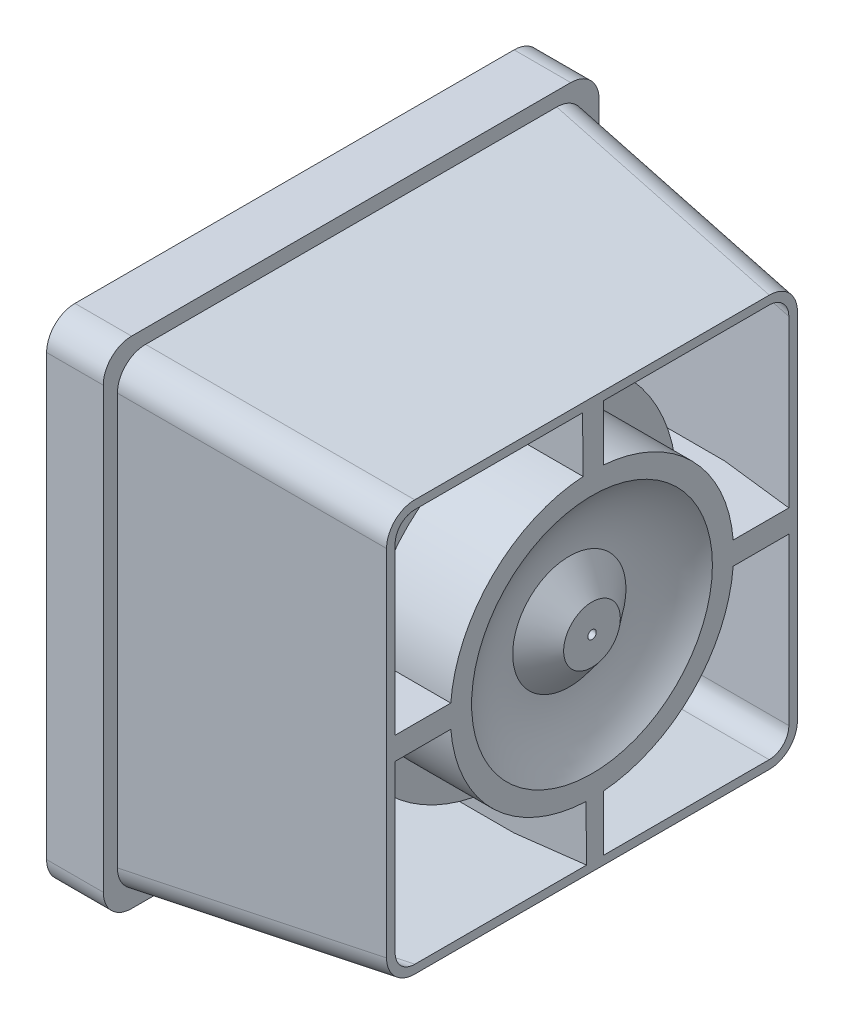
SolidWorks part; units mm, degrees
ref_plane "Front Plane" through (0, 0, 0) normal (0, 0, 1) x (1, 0, 0)
ref_plane "Top Plane" through (0, 0, 0) normal (0, 1, 0) x (1, 0, 0)
ref_plane "Right Plane" through (0, 0, 0) normal (1, 0, 0) x (0, 0, -1)
sketch "Sketch1" plane through (0, 0, 0) normal (1, 0, 0) x (0, 0, -1)
  line L1 (-8.25, -8.25) -> (8.25, -8.25)
  line L2 (-8.25, -8.25) -> (-8.25, 8.25)
  line L3 (-8.25, 8.25) -> (8.25, 8.25)
  line L4 (8.25, -8.25) -> (8.25, 8.25)
  line L5 (-8.25, -8.25) -> (8.25, 8.25) construction
  line L6 (-8.25, 8.25) -> (8.25, -8.25) construction
  point P0 (0, 0)
  dimension "D1" = 16.5
ref_plane "Plane1" through (8.5, 0, 0) normal (-1, 0, 0) x (0, 0, 1)
sketch "Sketch2" plane through (8.5, 0, 0) normal (-1, 0, 0) x (0, 0, 1)
  line L1 (-7.25, -7.25) -> (7.25, -7.25)
  line L2 (-7.25, -7.25) -> (-7.25, 7.25)
  line L3 (-7.25, 7.25) -> (7.25, 7.25)
  line L4 (7.25, -7.25) -> (7.25, 7.25)
  line L5 (-7.25, -7.25) -> (7.25, 7.25) construction
  line L6 (-7.25, 7.25) -> (7.25, -7.25) construction
  point P0 (0, 0)
  dimension "D1" = 14.5
loft "Loft1" add profiles "Sketch1", "Sketch2" connector at (0, -8.25, 8.25) connector at (8.5, -7.25, 7.25)
fillet "Fillet1" radius 1 4 edges
shell "Shell4" thickness 0.3 removed face at (8.5, 0, 0) removed face at (0, 0, 0)
sketch "Sketch3" plane through (0, 0, 0) normal (1, 0, 0) x (0, 0, -1)
  line L1 (-8.75, -8.75) -> (8.75, -8.75)
  line L2 (-8.75, -8.75) -> (-8.75, 8.75)
  line L3 (-8.75, 8.75) -> (8.75, 8.75)
  line L4 (8.75, -8.75) -> (8.75, 8.75)
  line L5 (-8.75, -8.75) -> (8.75, 8.75) construction
  line L6 (-8.75, 8.75) -> (8.75, -8.75) construction
  point P0 (0, 0)
  dimension "D1" = 17.5
extrude "Boss-Extrude1" add sketch "Sketch3" against normal blind 2
fillet "Fillet2" radius 1 4 edges at (-1, -8.75, -8.75) (-1, -8.75, 8.75) (-1, 8.75, 8.75) (-1, 8.75, -8.75)
sketch "Sketch5" plane through (0, 0, 0) normal (0, 0, 1) x (1, 0, 0)
  line L0 (0, -8.6833) -> (0, 8.6833) construction
  line L1 (0, 0) -> (0, 6)
  line L2 (0, 6) -> (5.5, 6)
  line L3 (5.5, 6) -> (5.5, 5)
  line L4 (5.5, 5) -> (8.5, 5)
  line L5 (8.5, 9.625) -> (8.5, -9.625) construction
  line L7 (8.5, 0) -> (0, 0)
  line L8 (8.5, 5) -> (8.5, 4.25)
  line L9 (7.7, 2) -> (8.5, 1)
  line L10 (8.5, 1) -> (8.5, 0)
  line L11 (7.7, 2) -> (7.7, 0.5026) construction
  arc A0 (8.5, 4.25) -> (7.7, 2) centre (11.2641, 2) ccw
  point P4 (0, 0)
  dimension "D7" = 2
  dimension "D1" = 6
  dimension "D2" = 3
  dimension "D3" = 5
  dimension "D4" = 0.75
  dimension "D5" = 1
  dimension "D6" = 0.8
revolve "Revolve3" add sketch "Sketch5" angle 360 about L7
sketch "Sketch12" plane through (0, 0, 0) normal (1, 0, 0) x (0, 0, -1)
  line L0 (0, 0) -> (13.1343, 0) construction
  line L1 (0, 0) -> (0, 13.47) construction
  line L2 (-0.4, 13.47) -> (-0.1105, -14.9416)
  line L3 (-0.1105, -14.9416) -> (0.4, -14.9416)
  line L4 (7.9479, -7.2527) -> (7.9479, 7.2527)
  line L5 (7.2527, 7.9479) -> (-7.2527, 7.9479)
  line L6 (-7.9479, 7.2527) -> (-7.9479, -7.2527)
  line L7 (-7.2527, -7.9479) -> (7.2527, -7.9479)
  line L8 (7.9479, -7.2527) -> (7.9479, 7.2527)
  line L9 (7.2527, 7.9479) -> (-7.2527, 7.9479)
  line L10 (-7.9479, 7.2527) -> (-7.9479, -7.2527)
  line L11 (-7.2527, -7.9479) -> (7.2527, -7.9479)
  line L12 (0.4, -14.9416) -> (0.4, 13.47)
  line L15 (13.1343, -0.4) -> (-14.0382, -0.4)
  line L16 (-14.0382, -0.4) -> (-14.0382, 0.4)
  line L17 (-14.0382, 0.4) -> (13.1343, 0.4)
  line L18 (0, 13.47) -> (0.4, 13.47)
  line L19 (-0.4, 13.47) -> (0, 13.47)
  line L20 (13.1343, 0.4) -> (13.1343, 0)
  line L21 (13.1343, 0) -> (13.1343, -0.4)
  line L22 (6.2568, -7.25) -> (-6.2568, -7.25) construction
  line L23 (-7.25, -6.2568) -> (-7.25, 6.2568) construction
  line L24 (7.25, 6.2568) -> (7.25, -6.2568) construction
  line L25 (-6.2568, 7.25) -> (6.2568, 7.25) construction
  line L26 (6.2568, -7.25) -> (-6.2568, -7.25)
  line L27 (-7.25, -6.2568) -> (-7.25, 6.2568)
  line L28 (7.25, 6.2568) -> (7.25, -6.2568)
  line L29 (-6.2568, 7.25) -> (6.2568, 7.25)
  circle A0 centre (0, 0) radius 5 construction
  circle A1 centre (0, 0) radius 5
  ellipse E4 centre (7.2431, -7.2431) end of major axis (6.7413, -6.7413) minor radius 0.7 (7.2527, -7.9479) -> (7.9479, -7.2527) ccw
  ellipse E5 centre (7.2431, 7.2431) end of major axis (6.7413, 6.7413) minor radius 0.7 (7.9479, 7.2527) -> (7.2527, 7.9479) ccw
  ellipse E6 centre (-7.2431, 7.2431) end of major axis (-6.7413, 6.7413) minor radius 0.7 (-7.2527, 7.9479) -> (-7.9479, 7.2527) ccw
  ellipse E7 centre (-7.2431, -7.2431) end of major axis (-6.7413, -6.7413) minor radius 0.7 (-7.9479, -7.2527) -> (-7.2527, -7.9479) ccw
  ellipse E8 centre (7.2431, -7.2431) end of major axis (6.7413, -6.7413) minor radius 0.7 (7.2527, -7.9479) -> (7.9479, -7.2527) ccw
  ellipse E9 centre (7.2431, 7.2431) end of major axis (6.7413, 6.7413) minor radius 0.7 (7.9479, 7.2527) -> (7.2527, 7.9479) ccw
  ellipse E10 centre (-7.2431, 7.2431) end of major axis (-6.7413, 6.7413) minor radius 0.7 (-7.2527, 7.9479) -> (-7.9479, 7.2527) ccw
  ellipse E11 centre (-7.2431, -7.2431) end of major axis (-6.7413, -6.7413) minor radius 0.7 (-7.9479, -7.2527) -> (-7.2527, -7.9479) ccw
  circle M23 centre (0, 0) radius 6
  dimension "D2" = 0.8
  dimension "D3" = 0.8
  dimension "D1" = 0
extrude "Boss-Extrude4" add sketch "Sketch12" along normal up to surface (8.5 mm away) contours L29 L2 L12 M23 | A1 L15 L17 M23 | L28 L17 L15 M23 | L27 L15 L17 M23 | L26 L12 L2 M23 | A1 L17 L15 M23 | A1 L2 L12 M23 | A1 L12 L2 M23 region at (0, 6.6249, -0.0351) region at (0, 5.4971, -0.0407) region at (0, 0, 6.6228) region at (0, 0, 5.4951) region at (0, 0, -5.4951) region at (0, 0, -6.6228) region at (0, -6.6211, -0.1028) region at (0, -5.4949, -0.0967) up to face at (8.5, 0, 0)
sketch "Sketch7" plane through (0, 0, 0) normal (0, 0, 1) x (1, 0, 0)
  line L0 (-2, 0) -> (-2, 4.5)
  line L1 (-2, -7.75) -> (-2, 7.75) construction
  line L2 (-2, 4.5) -> (-0.2, 4.5)
  line L3 (-0.2, 4.5) -> (0, 4.85)
  line L4 (0, -6) -> (0, 6) construction
  line L5 (0, 4.85) -> (0.5, 4.85)
  line L6 (0.5, 4.85) -> (1.6375, 4.2)
  line L7 (1.6375, 4.2) -> (6.7, 4.2)
  line L8 (6.7, 4.2) -> (6.7, 3.5)
  line L9 (6.7, 3.5) -> (3.1, 3.5)
  line L10 (3.1, 3.5) -> (3.1, 2.5)
  line L11 (3.1, 2.5) -> (6.7, 2.5)
  line L12 (6.7, 2.5) -> (6.7, 0)
  line L13 (6.7, 0) -> (-2, 0)
  line L14 (8.5, 9.0751) -> (8.5, -9.0751) construction
  dimension "D1" = 4.5
  dimension "D2" = 1.8
  dimension "D3" = 0.35
  dimension "D4" = 60.255
  dimension "D5" = 0.5
  dimension "D6" = 29.745
  dimension "D7" = 4.2
  dimension "D8" = 1.8
  dimension "D9" = 2.5
  dimension "D10" = 3.6
  dimension "D11" = 1
revolve "Cut-Revolve2" cut sketch "Sketch7" angle 360 about L13
fillet "Fillet4" radius 0.5 1 edges at (3.1, 2.5, 0)
sketch "Sketch9" plane through (6.7, 0, 0) normal (-1, 0, 0) x (0, 0, 1)
  line L0 (0, 0) -> (0, 2) construction
  line L1 (0, 0) -> (0, -2) construction
  line L2 (-0.75, 2) -> (0.75, 2)
  line L3 (0.75, 2) -> (0.75, 0)
  line L4 (-0.75, 2) -> (-0.75, 0)
  line L5 (-0.75, 0) -> (-0.75, -1.25)
  circle A0 centre (0, 0) radius 0.75
  circle A1 centre (0, -1.5714) radius 0.4286
  arc A2 (-0.75, -1.25) -> (0, -2) centre (0, -1.25) ccw
  arc A3 (0.4286, -1.5714) -> (-0.21, -0.72) centre (-0.4583, -1.5714) ccw
  point P8 (0, 2)
  dimension "D2" = 1.5
  dimension "D1" = 4
extrude "Cut-Extrude1" cut sketch "Sketch9" against normal blind 0.5 contours A0 L3 L2 L4 | A0 | A1 A3 A0 L5 A2 | A1 L3 region at (6.7, 1.2846, 0) region at (6.7, -1.06, -0.3897) region at (6.7, 0, 0) region at (6.7, -1.5714, 0)
sketch "Sketch10" plane through (0, 0, 0) normal (0, 0, 1) x (1, 0, 0)
  line L0 (8.5, 0) -> (6.3722, 0)
  line L1 (8.5, 9.0751) -> (8.5, -9.0751) construction
  line L2 (6.3722, 0) -> (6.3722, 0.75)
  line L3 (6.3722, 0.75) -> (7.2, 0.75)
  line L4 (7.2, 2) -> (7.2, -1.25) construction
  line L5 (7.2, 0.75) -> (7.5464, 0.15)
  line L6 (7.5464, 0.15) -> (8.5, 0.15)
  line L7 (8.5, 0.15) -> (8.5, 0)
  dimension "D1" = 0.75
  dimension "D2" = 30
  dimension "D3" = 0.15
revolve "Cut-Revolve3" cut sketch "Sketch10" angle 360 about L0
